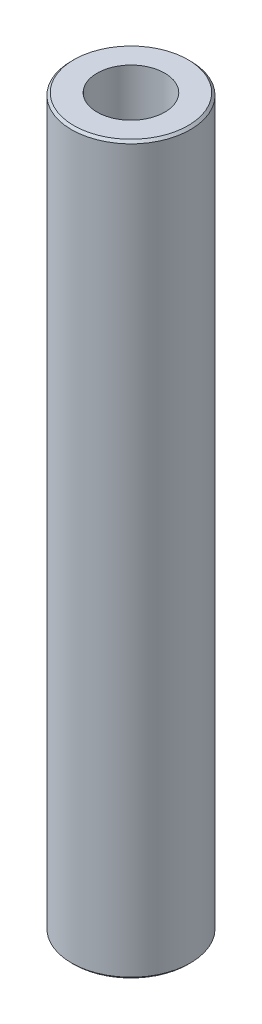
SolidWorks part; units mm, degrees
ref_plane "Front Plane" through (0, 0, 0) normal (0, 0, 1) x (1, 0, 0)
ref_plane "Top Plane" through (0, 0, 0) normal (0, 1, 0) x (1, 0, 0)
ref_plane "Right Plane" through (0, 0, 0) normal (1, 0, 0) x (0, 0, -1)
sketch "Sketch1" plane through (0, 0, 0) normal (0, 1, 0) x (1, 0, 0)
  circle A0 centre (0, 0) radius 7.5
  dimension "SHAFT_OD" = 15
extrude "Boss-Extrude1" add sketch "Sketch1" along normal blind 91.6175
sketch "Sketch2" plane through (0, 0, 0) normal (0, 1, 0) x (1, 0, 0)
  circle A0 centre (0, 0) radius 4.2671
  dimension "BORE_D" = 8.5342
extrude "Cut-Extrude1" cut sketch "Sketch2" along normal through all
chamfer "Chamfer1" distance 0.2948 angle 45 2 edges at (0, 91.6175, 7.5) (0, 0, 7.5)
